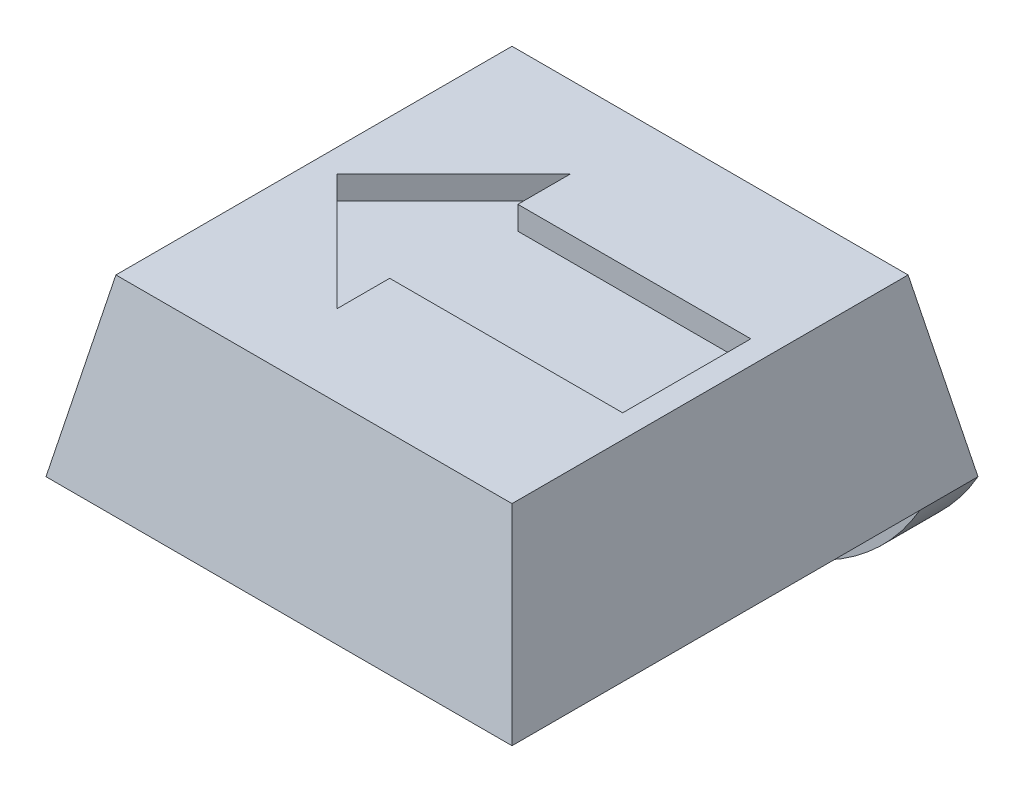
SolidWorks part; units mm, degrees
ref_plane "Front Plane" through (0, 0, 0) normal (0, 0, 1) x (1, 0, 0)
ref_plane "Top Plane" through (0, 0, 0) normal (0, 1, 0) x (1, 0, 0)
ref_plane "Right Plane" through (0, 0, 0) normal (1, 0, 0) x (0, 0, -1)
sketch "Sketch1" plane through (0, 0, 0) normal (0, 1, 0) x (1, 0, 0)
  line L1 (0, 0) -> (8, 0)
  line L2 (0, 0) -> (0, 8)
  line L3 (0, 8) -> (8, 8)
  line L4 (8, 0) -> (8, 8)
  dimension "D1" = 8
  dimension "D2" = 8
extrude "Boss-Extrude1" add sketch "Sketch1" along normal blind 3
sketch "Sketch2" plane through (0, 0, 0) normal (0, 0, 1) x (1, 0, 0)
  line L0 (0, 0) -> (0.6, 3)
  line L1 (0, 3) -> (8, 3) construction
  line L2 (0.6, 3) -> (0, 3)
  line L3 (0, 3) -> (0, 0)
  line L4 (8, 0) -> (7.4, 3)
  line L5 (7.4, 3) -> (8, 3)
  line L6 (8, 3) -> (8, 0)
  dimension "D1" = 0.6
  dimension "D2" = 0.6
extrude "Cut-Extrude1" cut sketch "Sketch2" against normal through all both and the other way through all
sketch "Sketch3" plane through (0, 0, 0) normal (1, 0, 0) x (0, 0, -1)
  line L0 (0, 0) -> (0.6, 3)
  line L1 (8, 3) -> (0, 3) construction
  line L2 (0.6, 3) -> (0, 3)
  line L3 (0, 3) -> (0, 0)
  line L4 (8, 3) -> (7.4, 3)
  line L5 (7.4, 3) -> (8, 0)
  line L6 (8, 3) -> (8, 0)
  dimension "D1" = 0.6
  dimension "D2" = 0.6
extrude "Cut-Extrude2" cut sketch "Sketch3" along normal blind 11
sketch "Sketch4" plane through (0, 0, 0) normal (0, -1, 0) x (1, 0, 0)
  line L0 (8, 0) -> (8, -8) construction
  line L3 (0, 0) -> (8, 0) construction
  circle A0 centre (4, -3.75) radius 1.75
  dimension "D1" = 3.5
  dimension "D2" = 4
  dimension "D3" = 3.75
extrude "Cut-Extrude3" cut sketch "Sketch4" against normal blind 0.4
sketch "Sketch5" plane through (0, 0, 0) normal (0, -1, 0) x (1, 0, 0)
  line L0 (8, 0) -> (8, -8) construction
  line L1 (0, -8) -> (8, -8)
  line L2 (0, -8) -> (0, -7)
  line L3 (0, -7) -> (8, -7)
  line L4 (8, -8) -> (8, -7)
  dimension "D1" = 1
extrude "Boss-Extrude2" add sketch "Sketch5" along normal blind 2
fillet "Fillet1" radius 4 2 edges at (8, -2, -7.5) (0, -2, -7.5)
sketch "Sketch6" plane through (0, 3, 0) normal (0, 1, 0) x (1, 0, 0)
  line L0 (3, 5.1) -> (3, 6)
  line L5 (3, 5.1) -> (7, 5.1)
  line L6 (3, 5.1) -> (3, 2.9)
  line L7 (3, 2.9) -> (7, 2.9)
  line L12 (7, 5.1) -> (7, 2.9)
  line L13 (3, 6) -> (1, 4)
  line L14 (1, 4) -> (3, 2)
  line L15 (3, 2) -> (3, 2.9)
  line L16 (7.4, 7.4) -> (0.6, 7.4) construction
  line L17 (7.4, 0.6) -> (0.6, 0.6) construction
  line L18 (7.4, 7.4) -> (7.4, 0.6) construction
  line L19 (0.6, 7.4) -> (0.6, 0.6) construction
  point P15 (0.6, 4)
  dimension "D1" = 4
  dimension "D2" = 1.4
  dimension "D3" = 1.4
  dimension "D4" = 0.4
  dimension "D5" = 0.4
  dimension "D6" = 2.3
  dimension "D7" = 2.3
  dimension "D8" = 0
extrude "Cut-Extrude4" cut sketch "Sketch6" against normal blind 0.4 contours L14 L15 L6 L0 L13 | L12 L5 L6 L7 region at (2.3333, 3, -4) region at (5, 3, -4)
